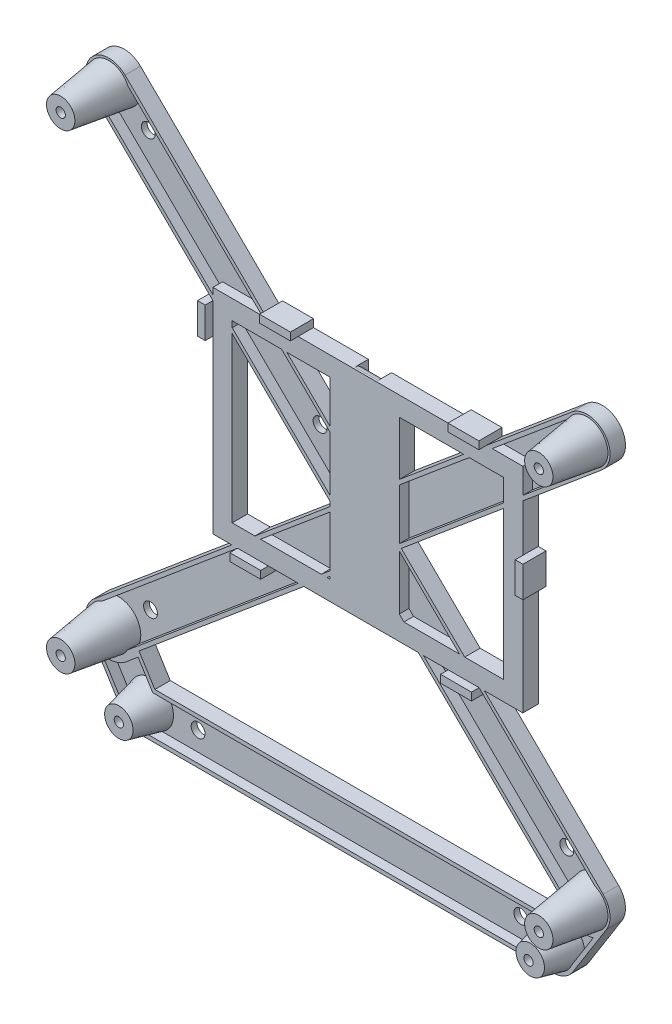
SolidWorks part; units mm, degrees
ref_plane "Front Plane" through (0, 0, 0) normal (0, 0, 1) x (1, 0, 0)
ref_plane "Top Plane" through (0, 0, 0) normal (0, 1, 0) x (1, 0, 0)
ref_plane "Right Plane" through (0, 0, 0) normal (1, 0, 0) x (0, 0, -1)
sketch "Guide Sketch" plane through (0, 0, 0) normal (0, 0, 1) x (1, 0, 0)
  line L1 (0, 0) -> (170, 0)
  line L2 (0, 0) -> (0, 170)
  line L3 (0, 170) -> (170, 170)
  line L4 (170, 0) -> (170, 170)
  line L5 (40.64, 119.2) -> (142.74, 119.2)
  line L6 (40.64, 119.2) -> (40.64, 48.842)
  line L7 (40.64, 48.842) -> (142.74, 48.842)
  line L8 (142.74, 119.2) -> (142.74, 48.842)
  line L9 (10.922, -6.35) -> (159.122, -6.35)
  line L10 (10.922, -6.35) -> (10.922, -31.75)
  line L11 (10.922, -31.75) -> (159.122, -31.75)
  line L12 (159.122, -6.35) -> (159.122, -31.75)
  circle A0 centre (6.35, 159.84) radius 1.98
  circle A1 centre (6.35, 4.9) radius 1.98
  circle A2 centre (163.83, 4.9) radius 1.98
  circle A3 centre (163.83, 136.98) radius 1.98
  circle A4 centre (17.272, -12.7) radius 2
  circle A5 centre (152.772, -12.7) radius 2
  dimension "D3" = 3.96
  dimension "D16" = 4
  dimension "D17" = 4
  dimension "D1" = 170
  dimension "D2" = 170
  dimension "D4" = 6.35
  dimension "D5" = 10.16
  dimension "D6" = 154.94
  dimension "D7" = 6.35
  dimension "D8" = 157.48
  dimension "D9" = 22.86
  dimension "D10" = 102.1
  dimension "D11" = 70.358
  dimension "D12" = 40.64
  dimension "D13" = 50.8
  dimension "D14" = 25.4
  dimension "D15" = 148.2
  dimension "D18" = 6.35
  dimension "D19" = 6.35
  dimension "D20" = 6.35
  dimension "D21" = 6.35
  dimension "D22" = 6.35
  dimension "D23" = 10.922
sketch "Sketch11" plane through (0, 0, 0) normal (0, 0, 1) x (1, 0, 0)
  line L0 (6.35, 159.84) -> (163.83, 4.9) construction
  line L1 (11.6942, 165.2718) -> (169.1742, 10.3318)
  line L2 (1.0058, 154.4082) -> (158.4858, -0.5318)
  line L3 (6.35, 4.9) -> (163.83, 136.98) construction
  line L4 (1.4533, 10.7384) -> (158.9333, 142.8184)
  line L5 (11.2467, -0.9384) -> (168.7267, 131.1416)
  arc A0 (11.6942, 165.2718) -> (1.0058, 154.4082) centre (6.35, 159.84) ccw
  arc A1 (158.4858, -0.5318) -> (169.1742, 10.3318) centre (163.83, 4.9) ccw
  arc A2 (1.4533, 10.7384) -> (11.2467, -0.9384) centre (6.35, 4.9) ccw
  arc A3 (168.7267, 131.1416) -> (158.9333, 142.8184) centre (163.83, 136.98) ccw
  point P4 (85.09, 82.37)
  point P9 (85.09, 70.94)
  dimension "D1" = 7.62
  dimension "D2" = 7.62
extrude "X Base" add sketch "Sketch11" along normal blind 1.905 contours L2 A1 L1 L5 | L2 L5 L1 L4 | L4 A2 L5 L2 | L5 A3 L4 L1 | L1 A0 L2 L4 region at (43.9971, 122.8223, 0) region at (132.8193, 110.9971, 0) region at (91.3613, 76.1998, 0) region at (132.4537, 35.7442, 0) region at (43.6318, 36.1464, 0)
sketch "Sketch12" plane through (0, 0, 1.905) normal (0, 0, 1) x (1, 0, 0)
  line L8 (90.9529, 65.9119) -> (158.4858, -0.5318)
  line L9 (169.1742, 10.3318) -> (102.6832, 75.7503)
  line L10 (102.6832, 75.7503) -> (168.7267, 131.1416)
  line L11 (158.9333, 142.8184) -> (91.7698, 86.4877)
  line L12 (91.7698, 86.4877) -> (11.6942, 165.2718)
  line L13 (1.0058, 154.4082) -> (80.0394, 76.6493)
  line L14 (80.0394, 76.6493) -> (1.4533, 10.7384)
  line L15 (11.2467, -0.9384) -> (90.9529, 65.9119)
  line L16 (90.9529, 65.9119) -> (158.4858, -0.5318)
  line L17 (169.1742, 10.3318) -> (102.6832, 75.7503)
  line L18 (102.6832, 75.7503) -> (168.7267, 131.1416)
  line L19 (158.9333, 142.8184) -> (91.7698, 86.4877)
  line L20 (91.7698, 86.4877) -> (11.6942, 165.2718)
  line L21 (1.0058, 154.4082) -> (80.0394, 76.6493)
  line L22 (80.0394, 76.6493) -> (1.4533, 10.7384)
  line L23 (11.2467, -0.9384) -> (90.9529, 65.9119)
  line L56 (91.0172, 67.5321) -> (159.3274, 0.3236)
  line L57 (168.3326, 9.4764) -> (100.9002, 75.8211)
  line L58 (100.9002, 75.8211) -> (167.9556, 132.0611)
  line L59 (159.7044, 141.8989) -> (91.7055, 84.8676)
  line L60 (91.7055, 84.8676) -> (10.8526, 164.4164)
  line L61 (1.8474, 155.2636) -> (81.8224, 76.5786)
  line L62 (81.8224, 76.5786) -> (2.2244, 9.8189)
  line L63 (10.4756, -0.0189) -> (91.0172, 67.5321)
  line L64 (91.0172, 67.5321) -> (159.3274, 0.3236)
  line L65 (168.3326, 9.4764) -> (100.9002, 75.8211)
  line L66 (100.9002, 75.8211) -> (167.9556, 132.0611)
  line L67 (159.7044, 141.8989) -> (91.7055, 84.8676)
  line L68 (91.7055, 84.8676) -> (10.8526, 164.4164)
  line L69 (1.8474, 155.2636) -> (81.8224, 76.5786)
  line L70 (81.8224, 76.5786) -> (2.2244, 9.8189)
  line L71 (10.4756, -0.0189) -> (91.0172, 67.5321)
  arc A4 (158.4858, -0.5318) -> (169.1742, 10.3318) centre (163.83, 4.9) ccw
  arc A5 (168.7267, 131.1416) -> (158.9333, 142.8184) centre (163.83, 136.98) ccw
  arc A6 (11.6942, 165.2718) -> (1.0058, 154.4082) centre (6.35, 159.84) ccw
  arc A7 (1.4533, 10.7384) -> (11.2467, -0.9384) centre (6.35, 4.9) ccw
  arc A8 (158.4858, -0.5318) -> (169.1742, 10.3318) centre (163.83, 4.9) ccw
  arc A9 (168.7267, 131.1416) -> (158.9333, 142.8184) centre (163.83, 136.98) ccw
  arc A10 (11.6942, 165.2718) -> (1.0058, 154.4082) centre (6.35, 159.84) ccw
  arc A11 (1.4533, 10.7384) -> (11.2467, -0.9384) centre (6.35, 4.9) ccw
  arc A28 (159.3274, 0.3236) -> (168.3326, 9.4764) centre (163.83, 4.9) ccw
  arc A29 (167.9556, 132.0611) -> (159.7044, 141.8989) centre (163.83, 136.98) ccw
  arc A30 (10.8526, 164.4164) -> (1.8474, 155.2636) centre (6.35, 159.84) ccw
  arc A31 (2.2244, 9.8189) -> (10.4756, -0.0189) centre (6.35, 4.9) ccw
  arc A32 (159.3274, 0.3236) -> (168.3326, 9.4764) centre (163.83, 4.9) ccw
  arc A33 (167.9556, 132.0611) -> (159.7044, 141.8989) centre (163.83, 136.98) ccw
  arc A34 (10.8526, 164.4164) -> (1.8474, 155.2636) centre (6.35, 159.84) ccw
  arc A35 (2.2244, 9.8189) -> (10.4756, -0.0189) centre (6.35, 4.9) ccw
  dimension "D1" = 0
  dimension "D2" = 1.2
extrude "Drive Base" add sketch "Sketch12" along normal blind 3.175
sketch "Sketch13" plane through (0, 0, 0) normal (0, 0, 1) x (1, 0, 0)
  line L0 (46.99, 112.85) -> (46.99, 55.192)
  line L1 (40.64, 119.2) -> (142.74, 119.2)
  line L2 (40.64, 119.2) -> (40.64, 48.842)
  line L3 (40.64, 48.842) -> (142.74, 48.842)
  line L4 (142.74, 119.2) -> (142.74, 48.842)
  line L5 (46.99, 55.192) -> (136.39, 55.192)
  line L6 (136.39, 112.85) -> (136.39, 55.192)
  line L7 (46.99, 112.85) -> (136.39, 112.85)
  dimension "D1" = 6.35
extrude "Boss-Extrude8" add sketch "Sketch13" along normal blind 5.08
sketch "Sketch14" plane through (0, 0, 0) normal (0, 0, 1) x (1, 0, 0)
  line L0 (142.74, 119.2) -> (142.74, 48.842) construction
  line L1 (58.5212, 119.2) -> (68.6812, 119.2)
  line L2 (58.5212, 119.2) -> (58.5212, 121.74)
  line L3 (58.5212, 121.74) -> (68.6812, 121.74)
  line L4 (68.6812, 119.2) -> (68.6812, 121.74)
  line L5 (130.7729, 119.2) -> (120.6129, 119.2)
  line L6 (130.7729, 119.2) -> (130.7729, 121.74)
  line L7 (130.7729, 121.74) -> (120.6129, 121.74)
  line L8 (120.6129, 119.2) -> (120.6129, 121.74)
  line L9 (48.7519, 48.842) -> (58.9119, 48.842)
  line L10 (48.7519, 48.842) -> (48.7519, 46.302)
  line L11 (48.7519, 46.302) -> (58.9119, 46.302)
  line L12 (58.9119, 48.842) -> (58.9119, 46.302)
  line L13 (128.3216, 48.842) -> (118.1616, 48.842)
  line L14 (128.3216, 48.842) -> (128.3216, 46.302)
  line L15 (128.3216, 46.302) -> (118.1616, 46.302)
  line L16 (118.1616, 48.842) -> (118.1616, 46.302)
  line L17 (142.74, 93.8) -> (145.28, 93.8)
  line L18 (142.74, 93.8) -> (142.74, 83.64)
  line L19 (142.74, 83.64) -> (145.28, 83.64)
  line L20 (145.28, 93.8) -> (145.28, 83.64)
  line L22 (40.64, 115.4133) -> (38.1, 115.4133)
  line L23 (40.64, 115.4133) -> (40.64, 105.2533)
  line L24 (40.64, 105.2533) -> (38.1, 105.2533)
  line L25 (38.1, 115.4133) -> (38.1, 105.2533)
  dimension "D1" = 2.54
  dimension "D2" = 2.54
  dimension "D3" = 2.54
  dimension "D4" = 10.16
  dimension "D5" = 10.16
  dimension "D6" = 10.16
  dimension "D7" = 10.16
  dimension "D8" = 10.16
  dimension "D9" = 10.16
  dimension "D10" = 25.4
  dimension "D11" = 2.54
extrude "Drive Tabs" add sketch "Sketch14" along normal blind 7.62
sketch "Sketch15" plane through (0, 0, 0) normal (0, 0, 1) x (1, 0, 0)
  line L0 (40.64, 119.2) -> (142.74, 119.2) construction
  line L1 (79.1619, 119.2) -> (102.0219, 119.2)
  line L2 (79.1619, 119.2) -> (79.1619, 48.842)
  line L3 (79.1619, 48.842) -> (102.0219, 48.842)
  line L4 (102.0219, 119.2) -> (102.0219, 48.842)
  line L5 (40.64, 48.842) -> (142.74, 48.842) construction
  line L7 (86.7819, 119.2) -> (94.4019, 119.2)
  line L8 (86.7819, 119.2) -> (86.7819, 48.842)
  line L9 (86.7819, 48.842) -> (94.4019, 48.842)
  line L10 (94.4019, 119.2) -> (94.4019, 48.842)
  dimension "D1" = 22.86
  dimension "D2" = 7.62
  dimension "D3" = 7.62
extrude "Tiedown Base" add sketch "Sketch15" along normal blind 5.08 contours L8 L1 L2 L3 | L1 L10 L3 L4 | L10 L1 L8 L3 region at (82.9719, 84.021, 0) region at (90.5919, 84.021, 0) region at (98.2119, 84.021, 0)
extrude "Tiedown Groove" cut sketch "Sketch15<3>" along normal blind 1.905 contours L10 L1 L8 L3 region at (90.5919, 84.021, 0)
sketch "Sketch15<3>" plane through (0, 0, 0) normal (0, 0, 1) x (1, 0, 0) same geometry as "Sketch15"
sketch "Sketch16" plane through (0, 0, 0) normal (0, 0, 1) x (1, 0, 0)
  circle A0 centre (6.35, 4.9) radius 7.62
  circle A1 centre (6.35, 159.84) radius 7.62
  circle A2 centre (163.83, 136.98) radius 7.62
  circle A3 centre (163.83, 4.9) radius 7.62
  arc A5 (11.6942, 165.2718) -> (1.0058, 154.4082) centre (6.35, 159.84) ccw construction
extrude "ITX Screw Bosses" add sketch "Sketch16" along normal blind 20.93 draft 8
sketch "Sketch17" plane through (0, 0, 1.905) normal (0, 0, 1) x (1, 0, 0)
  circle A0 centre (16.9022, 13.7502) radius 6.42
  circle A1 centre (16.1673, 150.181) radius 6.42
  circle A2 centre (153.2778, 128.1298) radius 6.42
  circle A3 centre (154.0127, 14.559) radius 6.42
  circle A4 centre (16.1673, 150.181) radius 2.286
  circle A5 centre (16.9022, 13.7502) radius 2.286
  circle A6 centre (154.0127, 14.559) radius 2.286
  circle A7 centre (153.2778, 128.1298) radius 2.286
  dimension "D1" = 4.572
extrude "Mounting Holes" cut sketch "Sketch17" against normal through all contours A5 | A4 | A7 | A6
sketch "Sketch19" plane through (0, 0, 0) normal (0, 0, 1) x (1, 0, 0)
  line L0 (17.272, -12.7) -> (152.772, -12.7) construction
  line L1 (17.272, -5.08) -> (152.772, -5.08)
  line L2 (17.272, -20.32) -> (152.772, -20.32)
  line L3 (152.772, -12.7) -> (163.83, 4.9) construction
  line L4 (146.3198, -8.6461) -> (157.3778, 8.9539)
  line L5 (159.2242, -16.7539) -> (170.2822, 0.8461)
  line L6 (6.35, 4.9) -> (17.272, -12.7) construction
  line L7 (12.8246, 8.9179) -> (23.7466, -8.6821)
  line L8 (-0.1246, 0.8821) -> (10.7974, -16.7179)
  arc A0 (17.272, -5.08) -> (17.272, -20.32) centre (17.272, -12.7) ccw
  arc A1 (152.772, -20.32) -> (152.772, -5.08) centre (152.772, -12.7) ccw
  arc A2 (146.3198, -8.6461) -> (159.2242, -16.7539) centre (152.772, -12.7) ccw
  arc A3 (170.2822, 0.8461) -> (157.3778, 8.9539) centre (163.83, 4.9) ccw
  arc A4 (12.8246, 8.9179) -> (-0.1246, 0.8821) centre (6.35, 4.9) ccw
  arc A5 (10.7974, -16.7179) -> (23.7466, -8.6821) centre (17.272, -12.7) ccw
  arc A6 (1.4533, 10.7384) -> (11.2467, -0.9384) centre (6.35, 4.9) ccw construction
  point P4 (85.022, -12.7)
  point P9 (158.301, -3.9)
  point P17 (11.811, -3.9)
extrude "Power Board Arm" add sketch "Sketch19" along normal up to surface (1.905 mm away) contours L7 A4 L8 A0 L1 | A0 A5 L7 L1 | A5 L2 A2 L4 L1 L7 | L5 A3 L4 L1 A1 | L4 A2 A1 L1 region at (8.543, 1.2485, 0) region at (17.3302, -12.5953, 0) region at (85.0237, -12.7205, 0) region at (161.5955, 1.2293, 0) region at (152.7151, -12.597, 0) up to face at (72.7377, 60.58, 1.905)
sketch "Sketch20" plane through (0, 0, 1.905) normal (0, 0, 1) x (1, 0, 0)
  line L16 (158.4858, -0.5318) -> (154.118, 3.7656)
  line L17 (154.118, 3.7656) -> (148.5604, -5.08)
  line L18 (148.5604, -5.08) -> (21.5113, -5.08)
  line L19 (21.5113, -5.08) -> (16.3072, 3.3059)
  line L20 (16.3072, 3.3059) -> (11.2467, -0.9384)
  line L21 (-0.1246, 0.8821) -> (10.7974, -16.7179)
  line L22 (17.272, -20.32) -> (152.772, -20.32)
  line L23 (159.2242, -16.7539) -> (170.2822, 0.8461)
  line L24 (158.4858, -0.5318) -> (154.118, 3.7656)
  line L25 (154.118, 3.7656) -> (148.5604, -5.08)
  line L26 (148.5604, -5.08) -> (21.5113, -5.08)
  line L27 (21.5113, -5.08) -> (16.3072, 3.3059)
  line L28 (16.3072, 3.3059) -> (11.2467, -0.9384)
  line L29 (-0.1246, 0.8821) -> (10.7974, -16.7179)
  line L30 (17.272, -20.32) -> (152.772, -20.32)
  line L31 (159.2242, -16.7539) -> (170.2822, 0.8461)
  line L56 (157.5951, -1.4371) -> (154.3532, 1.7526)
  line L57 (154.3532, 1.7526) -> (149.2623, -6.35)
  line L58 (149.2623, -6.35) -> (20.8047, -6.35)
  line L59 (20.8047, -6.35) -> (16.0007, 1.3913)
  line L60 (16.0007, 1.3913) -> (12.0628, -1.9114)
  line L61 (4.2351, -3.7348) -> (11.8765, -16.0483)
  line L62 (17.272, -19.05) -> (152.772, -19.05)
  line L63 (158.1488, -16.0782) -> (165.8968, -3.7464)
  line L64 (157.5951, -1.4371) -> (154.3532, 1.7526)
  line L65 (154.3532, 1.7526) -> (149.2623, -6.35)
  line L66 (149.2623, -6.35) -> (20.8047, -6.35)
  line L67 (20.8047, -6.35) -> (16.0007, 1.3913)
  line L68 (16.0007, 1.3913) -> (12.0628, -1.9114)
  line L69 (4.2351, -3.7348) -> (11.8765, -16.0483)
  line L70 (17.272, -19.05) -> (152.772, -19.05)
  line L71 (158.1488, -16.0782) -> (165.8968, -3.7464)
  arc A8 (-0.1246, 0.8821) -> (11.2467, -0.9384) centre (6.35, 4.9) ccw
  arc A9 (10.7974, -16.7179) -> (17.272, -20.32) centre (17.272, -12.7) ccw
  arc A10 (152.772, -20.32) -> (159.2242, -16.7539) centre (152.772, -12.7) ccw
  arc A11 (158.4858, -0.5318) -> (170.2822, 0.8461) centre (163.83, 4.9) ccw
  arc A12 (-0.1246, 0.8821) -> (11.2467, -0.9384) centre (6.35, 4.9) ccw
  arc A13 (10.7974, -16.7179) -> (17.272, -20.32) centre (17.272, -12.7) ccw
  arc A14 (152.772, -20.32) -> (159.2242, -16.7539) centre (152.772, -12.7) ccw
  arc A15 (158.4858, -0.5318) -> (170.2822, 0.8461) centre (163.83, 4.9) ccw
  arc A28 (4.2351, -3.7348) -> (12.0628, -1.9114) centre (6.35, 4.9) ccw
  arc A29 (11.8765, -16.0483) -> (17.272, -19.05) centre (17.272, -12.7) ccw
  arc A30 (152.772, -19.05) -> (158.1488, -16.0782) centre (152.772, -12.7) ccw
  arc A31 (157.5951, -1.4371) -> (165.8968, -3.7464) centre (163.83, 4.9) ccw
  arc A32 (4.2351, -3.7348) -> (12.0628, -1.9114) centre (6.35, 4.9) ccw
  arc A33 (11.8765, -16.0483) -> (17.272, -19.05) centre (17.272, -12.7) ccw
  arc A34 (152.772, -19.05) -> (158.1488, -16.0782) centre (152.772, -12.7) ccw
  arc A35 (157.5951, -1.4371) -> (165.8968, -3.7464) centre (163.83, 4.9) ccw
  dimension "D1" = 0
  dimension "D2" = 1.27
extrude "Power Board Edges" add sketch "Sketch20" along normal up to surface (3.175 mm away) up to face at (149.8243, 125.215, 5.08)
sketch "Sketch18" plane through (0, 0, 20.93) normal (0, 0, 1) x (1, 0, 0)
  circle A0 centre (6.35, 4.9) radius 1.524
  circle A1 centre (6.35, 159.84) radius 1.524
  circle A2 centre (163.83, 136.98) radius 1.524
  circle A3 centre (163.83, 4.9) radius 1.524
  dimension "D1" = 3.048
extrude "ITX Screw Holes" cut sketch "Sketch18" against normal through all
sketch "Sketch21" plane through (0, 0, 0) normal (0, 0, 1) x (1, 0, 0)
  circle A0 centre (17.272, -12.7) radius 7.62
  circle A1 centre (152.772, -12.7) radius 7.62
extrude "Power Bosses" add sketch "Sketch21" along normal blind 12.7 draft 13
sketch "Sketch22" plane through (0, 0, 12.7) normal (0, 0, 1) x (1, 0, 0)
  circle A0 centre (17.272, -12.7) radius 1.524
  circle A1 centre (152.2079, -13.1946) radius 1.524
  circle A2 centre (6.35, 4.9) radius 1.524 construction
extrude "Power Screw Holes" cut sketch "Sketch22" against normal through all
sketch "Sketch23" plane through (0, 0, 1.905) normal (0, 0, 1) x (1, 0, 0)
  circle A0 centre (32.5802, -12.7) radius 6.35
  circle A1 centre (138.8698, -12.7) radius 6.35
  circle A2 centre (138.8698, -12.7) radius 2.286
  circle A3 centre (32.5802, -12.7) radius 2.286
  circle A4 centre (154.0127, 14.559) radius 2.286 construction
  circle A5 centre (16.9022, 13.7502) radius 2.286 construction
extrude "Power Mounting Holes" cut sketch "Sketch23" against normal through all contours A3 | A2
fillet "Fillet1" radius 2.54 2 edges at (90.5919, 119.2, 1.905) (90.5919, 48.842, 1.905)
sketch "Sketch24" plane through (0, 0, 1.905) normal (0, 0, 1) x (1, 0, 0)
  circle A0 centre (72.7419, 94.5189) radius 6.42
  circle A1 centre (72.7419, 94.5189) radius 2.286
  circle A2 centre (153.2778, 128.1298) radius 2.286 construction
extrude "Additional Mounting Hole" cut sketch "Sketch24" against normal blind 12.7 contours A1 region at (72.7419, 94.5189, 1.905)
